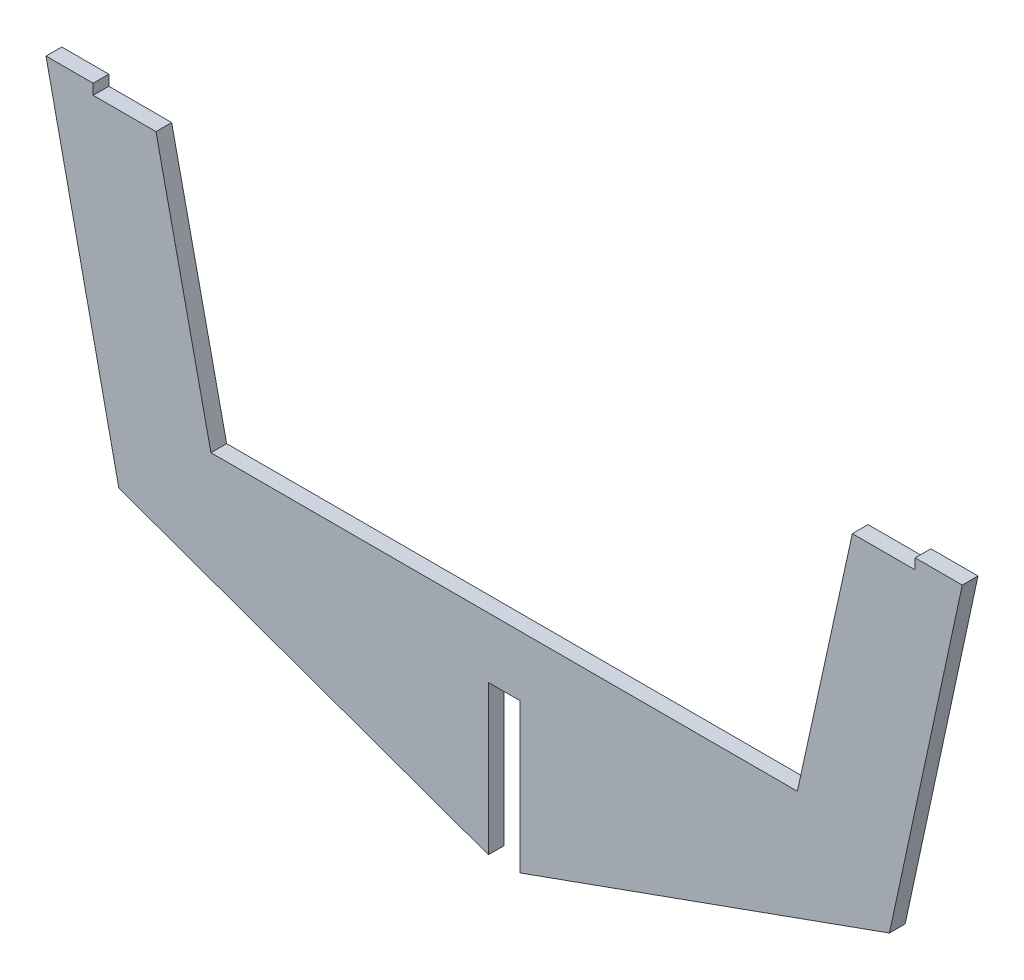
SolidWorks part; units mm, degrees
ref_plane "Plan de face" through (0, 0, 0) normal (0, 0, 1) x (1, 0, 0)
ref_plane "Plan de dessus" through (0, 0, 0) normal (0, 1, 0) x (1, 0, 0)
ref_plane "Plan de droite" through (0, 0, 0) normal (1, 0, 0) x (0, 0, -1)
sketch "Esquisse3" plane through (0, 0, 0) normal (0, 0, 1) x (1, 0, 0)
  line L43 (-28.5846, 68.1105) -> (-19.5846, 68.1105)
  line L44 (-19.5846, 68.1105) -> (-19.5846, 66.1105)
  line L45 (-19.5846, 66.1105) -> (-7.5846, 66.1105)
  line L46 (-7.5846, 66.1105) -> (2.9154, 18.2487)
  line L47 (2.9154, 18.2487) -> (45.961, 18.2487)
  line L48 (-28.5846, 68.1105) -> (-14.6725, 3.5934)
  line L49 (-14.6725, 3.5934) -> (34.9462, -14.2223)
  line L50 (34.9462, -14.2223) -> (55.9154, -21.7513)
  line L51 (55.9154, -21.7513) -> (55.9154, 6.7487)
  line L52 (61.9154, 6.7487) -> (55.9154, 6.7487)
  line L53 (71.8698, 18.2487) -> (45.961, 18.2487)
  line L54 (58.9154, 6.7487) -> (58.9154, 18.2487) construction
  line L55 (61.9154, -21.7513) -> (61.9154, 6.7487)
  line L56 (132.5033, 3.5934) -> (82.8846, -14.2223)
  line L57 (146.4154, 68.1105) -> (132.5033, 3.5934)
  line L58 (146.4154, 68.1105) -> (137.4154, 68.1105)
  line L59 (137.4154, 68.1105) -> (137.4154, 66.1105)
  line L60 (137.4154, 66.1105) -> (125.4154, 66.1105)
  line L61 (125.4154, 66.1105) -> (114.9154, 18.2487)
  line L62 (114.9154, 18.2487) -> (71.8698, 18.2487)
  line L63 (82.8846, -14.2223) -> (61.9154, -21.7513)
  dimension "D1" = 6
  dimension "D2" = 28.5
  dimension "D3" = 112
  dimension "D4" = 12
  dimension "D5" = 9
  dimension "D6" = 2
  dimension "D7" = 49
  dimension "D8" = 133
  dimension "D9" = 66
  dimension "D10" = 75
  dimension "D11" = 40
extrude "Boss.-Extru.3" add sketch "Esquisse3" along normal blind 3
